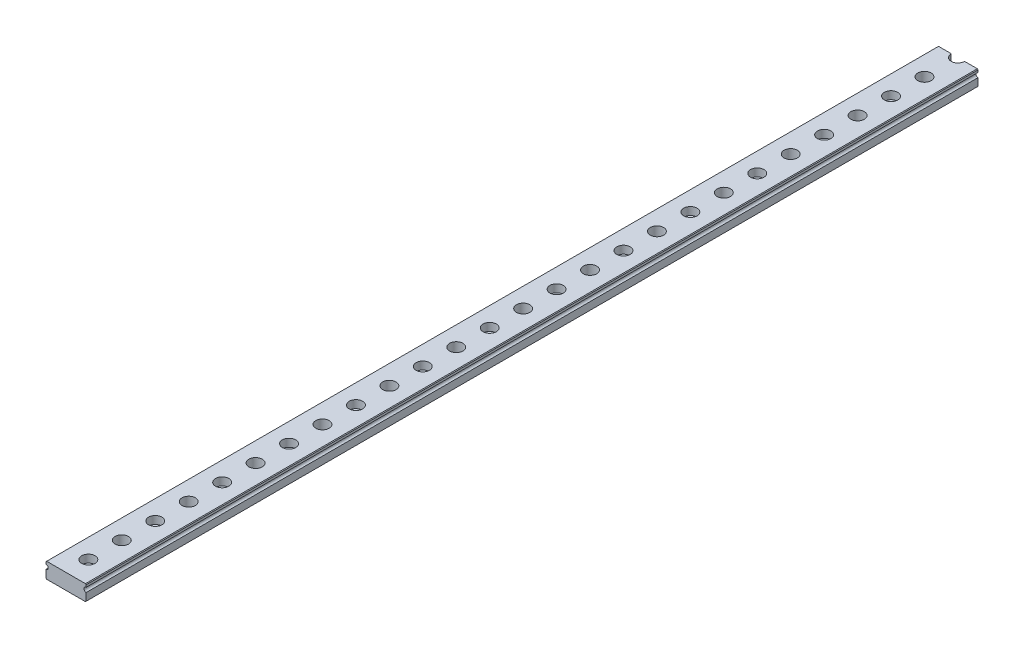
SolidWorks part; units mm, degrees
material "AISI 1020"
ref_plane "Front Plane" through (0, 0, 0) normal (0, 0, 1) x (1, 0, 0)
ref_plane "Top Plane" through (0, 0, 0) normal (0, 1, 0) x (1, 0, 0)
ref_plane "Right Plane" through (0, 0, 0) normal (1, 0, 0) x (0, 0, -1)
ref_plane "Plano1" through (0, 0, 0) normal (0, -1, 0) x (1, 0, 0)
sketch "Esboço1" plane through (0, 0, 0) normal (0, -1, 0) x (1, 0, 0)
  line L0 (-18, -400) -> (0, -400)
  line L1 (0, -400) -> (0, 0)
  line L2 (0, 0) -> (-18, 0)
  line L3 (-18, 0) -> (-18, -400)
  dimension "D1" = 400
  dimension "D2" = 18
extrude "Ressalto-extrusão1" add sketch "Esboço1" against normal blind 7
hole_wizard "Furo de diâmetro Ø2.0 (2)1" positions "Esboço5" profile "Esboço4" hole size "Ø2.0" standard "Ansi Metric" end condition through all
sketch "Esboço5" plane through (0, 0, -400) normal (0, 0, -1) x (-1, 0, 0)
  line L0 (0, 0) -> (18, 0) construction
  line L1 (18, 7) -> (18, 0) construction
  point P0 (0, 4.7)
  point P1 (18, 4.7)
  dimension "D1" = 18
  dimension "D2" = 4.7
sketch "Esboço4" plane through (0, 4.7, -400) normal (1, 0, 0) x (0, 1, 0)
  line L0 (0, 0) -> (0, 400)
  line L1 (0, 400) -> (1, 400)
  line L2 (1, 400) -> (1, 0)
  line L5 (1, 0) -> (0, 0)
  line L11 (0, -6.35) -> (0, 107.95) construction
  dimension "Thru Hole Dia." = 2
  dimension "Thru Hole Depth" = 400
hole_wizard "Furo de diâmetro Ø6.0 (6)1" positions "Esboço3" profile "Esboço2" hole size "Ø6.0" standard "Ansi Metric" end condition through all
sketch "Esboço3" plane through (0, 7, 0) normal (0, 1, 0) x (1, 0, 0)
  line L0 (0, 400) -> (0, 0) construction
  line L1 (0, 0) -> (-18, 0) construction
  point P0 (-9, 25)
  dimension "D3" = 9
  dimension "D4" = 25
sketch "Esboço2" plane through (-9, 7, -25) normal (1, 0, 0) x (0, 0, 1)
  line L0 (0, 0) -> (0, 7)
  line L1 (0, 7) -> (3, 7)
  line L2 (3, 7) -> (3, 0)
  line L5 (3, 0) -> (0, 0)
  line L11 (0, -6.35) -> (0, 107.95) construction
  dimension "Thru Hole Dia." = 6
  dimension "Thru Hole Depth" = 7
hole_wizard "Rebaixo para parafuso de máquina de cabeça sextavada de M31" positions "Esboço9" profile "Esboço8" counterbore size "M3" standard "Ansi Metric" end condition through all
sketch "Esboço9" plane through (0, 7, 0) normal (0, 1, 0) x (1, 0, 0)
  line L0 (0, 400) -> (0, 0) construction
  line L3 (0, 0) -> (-18, 0) construction
  point P2 (-9, 10)
  dimension "D3" = 9
  dimension "D6" = 10
sketch "Esboço8" plane through (-9, 7, -10) normal (1, 0, 0) x (0, 0, 1)
  line L0 (0, 0) -> (0, 7)
  line L1 (0, 7) -> (1.75, 7)
  line L3 (1.75, 7) -> (1.75, 3.5)
  line L4 (1.75, 3.5) -> (3, 3.5)
  line L5 (3, 3.5) -> (3, 0)
  line L7 (3, 0) -> (0, 0)
  line L11 (0, -6.35) -> (0, 107.95) construction
  dimension "Thru Hole Dia." = 3.5
  dimension "Thru Hole Depth" = 7
  dimension "C'Bore Dia." = 6
  dimension "C'Bore Depth" = 3.5
pattern_linear "Padrão linear1" count 13 spacing 30 along (0, 0, -1) of "Furo de diâmetro Ø6.0 (6)1"
pattern_linear "Padrão linear2" count 14 spacing 30 along (0, 0, -1) of "Rebaixo para parafuso de máquina de cabeça sextavada de M31"
chamfer "Chanfro1" distance 0.3 angle 45 4 edges at (-18, 7, -200) (0, 7, -200) (0, 0, -200) (-18, 0, -200)
ref_plane "Plane1" through (-9, 0, 0) normal (1, 0, 0) x (0, 0, -1)
ref_plane "Plane2" through (0, 0, -200) normal (0, 0, -1) x (-1, 0, 0)
